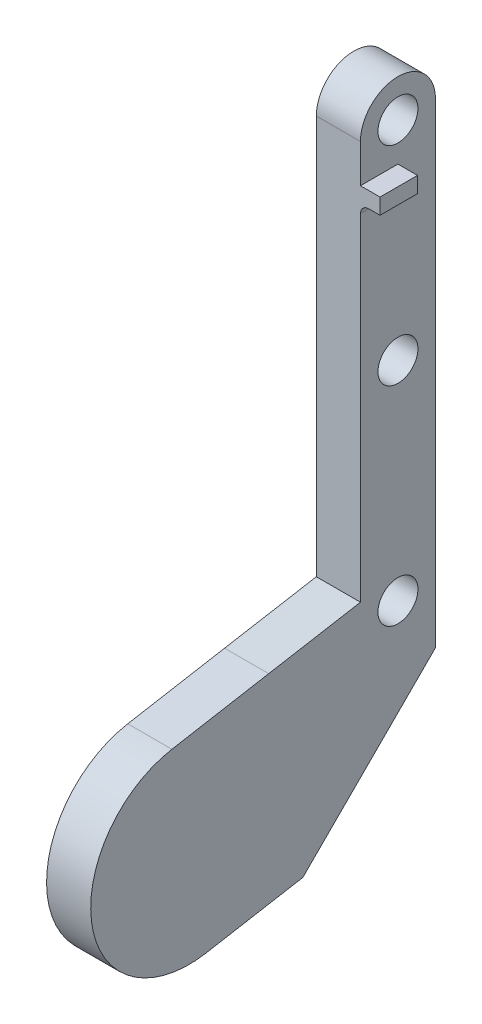
SolidWorks part; units mm, degrees
ref_plane "Front Plane" through (0, 0, 0) normal (0, 0, 1) x (1, 0, 0)
ref_plane "Top Plane" through (0, 0, 0) normal (0, 1, 0) x (1, 0, 0)
ref_plane "Right Plane" through (0, 0, 0) normal (1, 0, 0) x (0, 0, -1)
sketch "Sketch2" plane through (0, 0, 0) normal (1, 0, 0) x (0, 0, -1)
  line L0 (10.59, 0) -> (0, 0) construction
  line L1 (-9.41, -15) -> (-123.3736, -15) construction
  line L2 (-9.41, -15) -> (-9.41, 15) construction
  line L3 (-9.41, 15) -> (-123.3736, 15) construction
  line L4 (-123.3736, -15) -> (-123.3736, 15) construction
  line L5 (10.59, 10) -> (-29.41, 10) construction
  line L6 (10.59, 10) -> (10.59, -10) construction
  line L7 (10.59, -10) -> (-29.41, -10) construction
  line L8 (-29.41, 10) -> (-29.41, -10) construction
  line L9 (-9.41, 10) -> (-9.41, -10) construction
  line L10 (8.59, 63.5) -> (18.59, 63.5) construction
  line L11 (-9.41, 15) -> (8.59, 15) construction
  line L12 (-9.41, 15) -> (-9.41, 112) construction
  line L13 (-9.41, 112) -> (8.59, 112) construction
  line L14 (8.59, 15) -> (8.59, 112) construction
  line L15 (18.59, 76) -> (18.59, 51) construction
  line L16 (18.59, 51) -> (8.59, 51) construction
  line L17 (18.59, 76) -> (8.59, 76) construction
  line L18 (18.59, 73) -> (8.59, 73) construction
  line L19 (18.59, 54) -> (8.59, 54) construction
  line L20 (13.59, 54) -> (13.59, 73) construction
  line L21 (20.59, 63.5) -> (18.59, 63.5) construction
  line L22 (25.09, 59) -> (18.59, 59) construction
  line L23 (25.09, 68) -> (18.59, 68) construction
  line L24 (-29.41, 0) -> (-123.3736, 0) construction
  circle A0 centre (0, 0) radius 9.8
  circle A1 centre (-7, 0) radius 1.45
  circle A2 centre (0, 7) radius 1.45
  circle A3 centre (7, 0) radius 1.45
  circle A4 centre (0, -7) radius 1.45
  circle A5 centre (25.09, 63.5) radius 4.5 construction
  circle A6 centre (25.09, 63.5) radius 2.5 construction
  point P30 (18.59, 63.5)
  point P39 (13.59, 63.5)
  point P47 (0, 0)
  dimension "D5" = 19.6
  dimension "D6" = 2.9
  dimension "D15" = 9
  dimension "D17" = 2
  dimension "D1" = 30
  dimension "D2" = 20
  dimension "D3" = 40
  dimension "D4" = 10.59
  dimension "D7" = 7
  dimension "D9" = 113.9636
  dimension "D10" = 97
  dimension "D11" = 18
  dimension "D12" = 25
  dimension "D13" = 10
  dimension "D14" = 19
  dimension "D16" = 2
  dimension "D8" = 4
sketch "Sketch1" plane through (0, 0, 0) normal (1, 0, 0) x (0, 0, -1)
  line L13 (9.5717, 13.6698) -> (-13.6698, 9.5717)
  line L14 (-13.6698, 9.5717) -> (-9.5717, -13.6698)
  line L15 (-9.5717, -13.6698) -> (13.6698, -9.5717)
  line L16 (13.6698, -9.5717) -> (9.5717, 13.6698)
  line L17 (-2.049, 11.6207) -> (-1.7018, 9.6511) construction
  line L18 (0, 0) -> (-1.7018, 9.6511) construction
  line L19 (-11.6207, -2.049) -> (-9.6511, -1.7018) construction
  line L20 (-9.6511, -1.7018) -> (0, 0) construction
  line L21 (10.59, 10) -> (-29.41, 10) construction
  line L22 (20.59, 63.5) -> (20.59, 15.5903)
  line L23 (29.59, 63.5) -> (29.59, 6.3485)
  line L24 (29.59, 6.3485) -> (13.6698, -9.5717)
  line L25 (20.59, 15.5903) -> (9.5717, 13.6698)
  line L26 (10.59, -10) -> (-29.41, -10) construction
  line L27 (25.09, 59) -> (18.59, 59) construction
  line L28 (20.59, 59) -> (25.09, 59)
  line L29 (20.59, 59) -> (20.59, 57)
  line L30 (20.59, 57) -> (25.09, 57)
  line L31 (25.09, 59) -> (25.09, 57)
  circle A2 centre (0, 0) radius 9.8
  circle A3 centre (-7, 0) radius 1.5
  circle A4 centre (0, 7) radius 1.5
  circle A5 centre (7, 0) radius 1.5
  circle A6 centre (0, -7) radius 1.5
  circle A7 centre (25.09, 63.5) radius 4.5 construction
  arc A8 (20.59, 63.5) -> (29.59, 63.5) centre (25.09, 63.5) cw
  arc A9 (-11.6207, -2.049) -> (-2.049, 11.6207) centre (0, 0) cw
  arc A10 (-11.6207, -2.049) -> (2.049, -11.6207) centre (0, 0) ccw
  circle A11 centre (25.09, 63.5) radius 2.5
  circle A12 centre (25.09, 38.5) radius 2.5
  circle A13 centre (25.09, 13.5) radius 2.5
  circle A14 centre (0, 0) radius 2.65
  point P20 (-1.7018, 9.6511)
  dimension "D1" = 2
  dimension "D2" = 19.6
  dimension "D3" = 3
  dimension "D10" = 5
  dimension "D13" = 5.3
  dimension "D4" = 7
  dimension "D6" = 10
  dimension "D7" = 15.9202
  dimension "D8" = 11.1844
  dimension "D9" = 45
  dimension "D12" = 25
  dimension "D14" = 2
  dimension "D11" = 3
  dimension "D5" = 4
extrude "Boss-Extrude1" add sketch "Sketch1" along normal mid plane 5.3 contours A9 A10 L15 L16 L13 A2 | A5 | A14 | A4 | A6 | A2 A14 A6 A5 A4 A3 | A8 L22 L28 L31 L30 L25 L16 L24 L23 A13 A12 A11 | L31 L28 L22 L30 | A3 region at (0, 1.9865, -11.266) region at (0, 25.6732, -22.494) region at (0, 58, -22.84) region at (0, 0, 9.5228) region at (0, 7, 0) region at (0, 0, -7) region at (0, -7, 0) region at (0, 0, 0)
extrude "Boss-Extrude2" add sketch "Sketch1<5>" along normal blind 5 contours L28 L31 L30 L29
sketch "Sketch1<5>" plane through (0, 0, 0) normal (1, 0, 0) x (0, 0, -1) same geometry as "Sketch1"
fillet "Fillet1" radius 1 1 edges at (2.65, 57, -22.84)
other "Move Face1" face at (2.65, 13.5, -27.59) face at (2.65, 38.5, -27.59) face at (2.65, 63.5, -27.59) offset 0.1 parameters "D1"=0.1
other "Move Face2" flip direction yes face at (3.825, 59, -22.84) offset 0.1 parameters "D1"=0.1
equation "\"DisplayHeight\"= 18mm"
equation "\"DisplayWidth\"= 93mm"
equation "\"DisplayTall\"= 97mm"
equation "\"boxWidth\" = 15cm"
equation "\"boxTall\" = 20cm"
equation "\"boxHeight\" =68.5cm"
